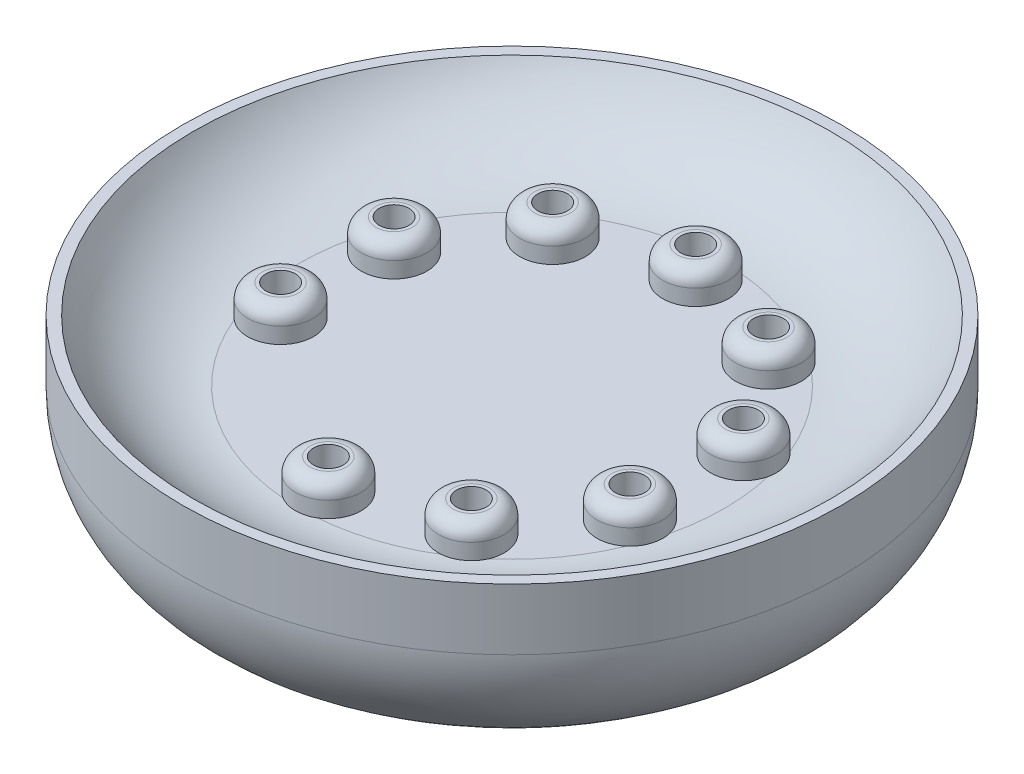
SolidWorks part; units mm, degrees
ref_plane "Plano frontal" through (0, 0, 0) normal (0, 0, 1) x (1, 0, 0)
ref_plane "Plano superior" through (0, 0, 0) normal (0, 1, 0) x (1, 0, 0)
ref_plane "Plano direito" through (0, 0, 0) normal (1, 0, 0) x (0, 0, -1)
sketch "Esboço1" plane through (0, 0, 0) normal (0, 1, 0) x (1, 0, 0)
  circle A0 centre (0, 0) radius 10.765
  dimension "D1" = 21.53
extrude "Ressalto-extrusão1" add sketch "Esboço1" along normal blind 6
fillet "Filete2" radius 4 1 edges at (0, 0, 10.765)
sketch "Esboço5" plane through (0, 6, 0) normal (0, 1, 0) x (1, 0, 0)
  circle A0 centre (0, 0) radius 10.405
  circle A1 centre (0, 0) radius 10.765 construction
  dimension "D1" = 0.36
extrude "Corte-extrusão2" cut sketch "Esboço5" against normal blind 2
fillet "Filete3" radius 4 1 edges at (0, 4, 10.405)
sketch "Esboço6" plane through (0, 4, 0) normal (0, 1, 0) x (1, 0, 0)
  circle A1 centre (0, 6) radius 0.485
  circle A2 centre (3.5267, 4.8541) radius 0.485
  circle A3 centre (5.7063, 1.8541) radius 0.485
  circle A4 centre (5.7063, -1.8541) radius 0.485
  circle A5 centre (3.5267, -4.8541) radius 0.485
  circle A6 centre (0, -6) radius 0.485
  circle A8 centre (-5.7063, -1.8541) radius 0.485
  circle A9 centre (-5.7063, 1.8541) radius 0.485
  circle A10 centre (-3.5267, 4.8541) radius 0.485
  circle A11 centre (-3.5267, -4.8541) radius 0.485 [skipped]
  point P26 (0, 0)
  dimension "D2" = 0.97
  dimension "D3" = 10
extrude "Corte-extrusão4" cut sketch "Esboço6" against normal blind 10 and the other way blind 14
sketch "Esboço7" plane through (0, 4, 0) normal (0, 1, 0) x (1, 0, 0)
  circle A1 centre (-3.5267, 4.8541) radius 1.0746
  circle A2 centre (0, 6) radius 1.0746
  circle A3 centre (3.5267, 4.8541) radius 1.0746
  circle A4 centre (5.7063, 1.8541) radius 1.0746
  circle A5 centre (5.7063, -1.8541) radius 1.0746
  circle A6 centre (3.5267, -4.8541) radius 1.0746
  circle A7 centre (0, -6) radius 1.0746
  circle A9 centre (-5.7063, -1.8541) radius 1.0746
  circle A10 centre (-5.7063, 1.8541) radius 1.0746
  circle A11 centre (-5.7063, 1.8541) radius 0.485
  circle A12 centre (-3.5267, 4.8541) radius 0.485
  circle A13 centre (0, 6) radius 0.485
  circle A14 centre (3.5267, 4.8541) radius 0.485
  circle A15 centre (5.7063, 1.8541) radius 0.485
  circle A16 centre (5.7063, -1.8541) radius 0.485
  circle A17 centre (3.5267, -4.8541) radius 0.485
  circle A18 centre (0, -6) radius 0.485
  circle A20 centre (-5.7063, -1.8541) radius 0.485
  arc A21 (-3.9072, -4.5534) -> (-3.1231, -5.1231) centre (-3.5267, -4.8541) ccw [skipped]
  arc A22 (-4.336, -4.1471) -> (-2.6042, -5.4054) centre (-3.5267, -4.8541) ccw [skipped]
  point P28 (0, 0)
  point P48 (0, 0)
  dimension "D1" = 10
  dimension "D2" = 10
extrude "Ressalto-extrusão2" add sketch "Esboço7" along normal blind 1
fillet "Filete5" radius 0.48 9 edges at (0, 5, -4.9254) (3.5267, 5, -3.7795) (5.7063, 5, -0.7795) (5.7063, 5, 2.9287) (3.5267, 5, 5.9287) (0, 5, 7.0746) (-5.7063, 5, 2.9287) (-5.7063, 5, -0.7795) (-3.5267, 5, -3.7795)
